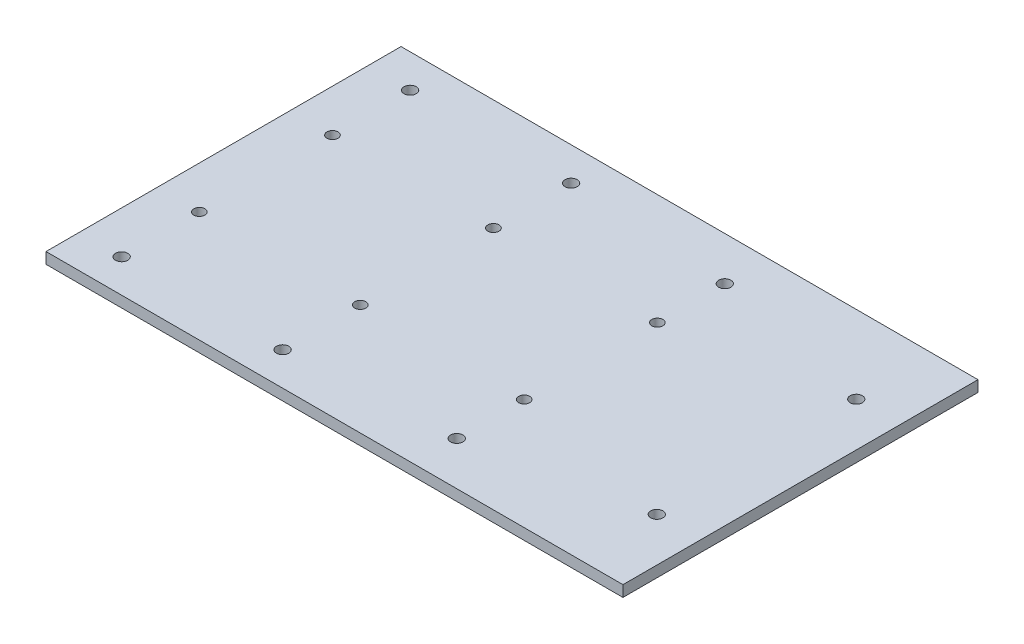
SolidWorks part; units mm, degrees
material "6061-T6 (SS)"
ref_plane "Front Plane" through (0, 0, 0) normal (0, 0, 1) x (1, 0, 0)
ref_plane "Top Plane" through (0, 0, 0) normal (0, 1, 0) x (1, 0, 0)
ref_plane "Right Plane" through (0, 0, 0) normal (1, 0, 0) x (0, 0, -1)
sketch "Sketch1" plane through (0, 0, 0) normal (0, 1, 0) x (1, 0, 0)
  line L1 (-165.1, -101.6) -> (165.1, -101.6)
  line L2 (-165.1, -101.6) -> (-165.1, 101.6)
  line L3 (-165.1, 101.6) -> (165.1, 101.6)
  line L4 (165.1, -101.6) -> (165.1, 101.6)
  line L5 (-165.1, -101.6) -> (165.1, 101.6) construction
  line L6 (-165.1, 101.6) -> (165.1, -101.6) construction
  point P0 (0, 0)
  dimension "D1" = 330.2
  dimension "D2" = 203.2
extrude "Boss-Extrude1" add sketch "Sketch1" along normal blind 6.35
sketch "Sketch2" plane through (0, 6.35, 0) normal (0, 1, 0) x (1, 0, 0)
  line L0 (-140.8516, 82.55) -> (-140.8516, -82.55) construction
  line L1 (-48.7159, 82.55) -> (-48.7159, -82.55) construction
  line L2 (45.0841, 76.699) -> (45.0841, -76.701) construction
  line L3 (-140.8516, 0) -> (45.0841, -0.001) construction
  line L4 (-140.8518, -38.1) -> (45.0839, -38.101) construction
  line L5 (-140.8514, 38.1) -> (45.0843, 38.099) construction
  point P0 (-140.8516, -82.55)
  point P1 (-48.7159, -82.55)
  point P3 (45.0841, -76.701)
  point P5 (45.0841, 76.699)
  point P7 (-48.7159, 82.55)
  point P9 (-140.8516, 82.55)
  point P25 (-48.7159, -38.1005)
  point P26 (-140.8518, -38.1)
  point P27 (-48.7159, 38.0995)
  point P28 (45.0843, 38.099)
  point P29 (45.0839, -38.101)
  point P30 (-140.8514, 38.1)
  point P31 (139.9541, 57.072)
  point P32 (139.9541, -57.072)
  point P33 (0, 0)
  point P36 (0, 0)
  point P37 (0, 0)
  point P38 (0, 0)
  dimension "D1" = 38.1
  dimension "D2" = 38.1
hole_wizard "1/4 (0.25) Press Dowel Hole1" positions "Sketch3" profile "Sketch4" hole size "1/4" standard "ANSI Inch" end condition through all
sketch "Sketch3" plane through (0, 6.35, 0) normal (0, 1, 0) x (1, 0, 0)
  point P0 (-140.8514, 38.1)
  point P3 (-140.8518, -38.1)
  point P6 (-48.7159, -38.1005)
  point P9 (-48.7159, 38.0995)
  point P12 (45.0843, 38.099)
  point P15 (45.0839, -38.101)
sketch "Sketch4" plane through (-140.8514, 6.35, -38.1) normal (1, 0, 0) x (0, 0, 1)
  line L0 (0, 0) -> (0, 6.35)
  line L1 (0, 6.35) -> (3.175, 6.35)
  line L2 (3.175, 6.35) -> (3.175, 0)
  line L5 (3.175, 0) -> (0, 0)
  line L11 (0, -6.35) -> (0, 107.95) construction
  dimension "Thru Hole Dia." = 6.35
  dimension "Thru Hole Depth" = 6.35
hole_wizard "M8x1.0 Tapped Hole1" positions "Sketch5" profile "Sketch6" tap size "M8x1.0" standard "ANSI Metric" end condition through all
sketch "Sketch5" plane through (0, 6.35, 0) normal (0, 1, 0) x (1, 0, 0)
  point P0 (-140.8516, 82.55)
  point P3 (-48.7159, 82.55)
  point P6 (45.0841, 76.699)
  point P9 (45.0841, -76.701)
  point P12 (-48.7159, -82.55)
  point P15 (-140.8516, -82.55)
  point P19 (139.9541, 57.072)
  point P22 (139.9541, -57.072)
sketch "Sketch6" plane through (-140.8516, 6.35, -82.55) normal (1, 0, 0) x (0, 0, 1)
  line L0 (0, 0) -> (0, 6.35)
  line L1 (0, 6.35) -> (3.5, 6.35)
  line L2 (3.5, 6.35) -> (3.5, 0)
  line L5 (3.5, 0) -> (0, 0)
  line L11 (0, -6.35) -> (0, 107.95) construction
  dimension "Thread Major Dia." = 7
  dimension "Thru Tap Drill Depth" = 6.35
sketch "Sketch7"
